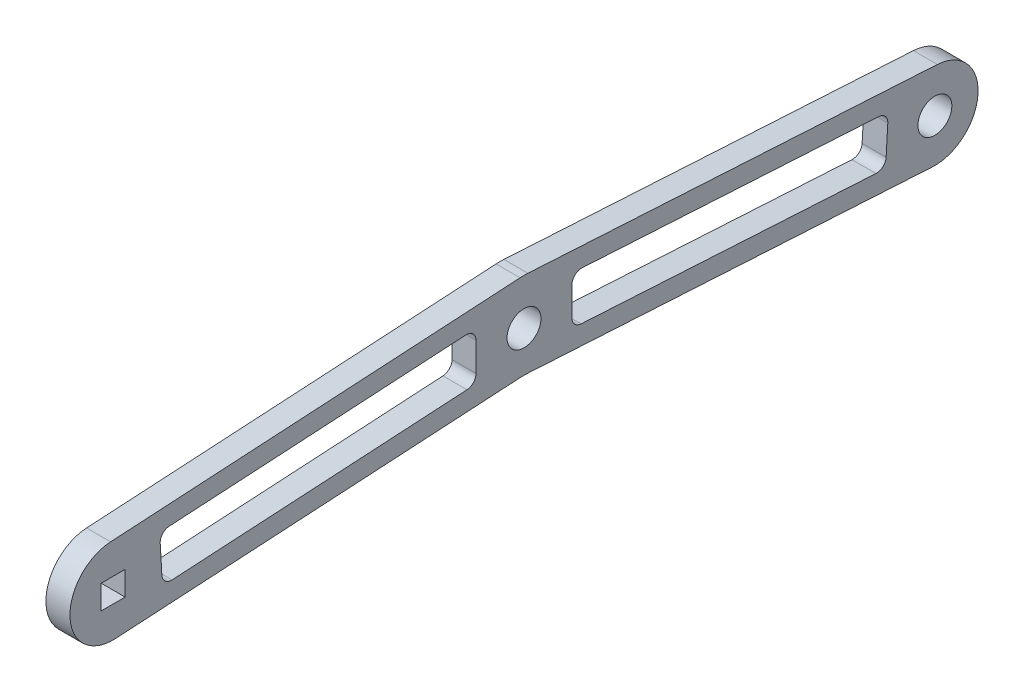
SolidWorks part; units mm, degrees
material "Custom Plastic"
ref_plane "Front Plane" through (0, 0, 0) normal (0, 0, 1) x (1, 0, 0)
ref_plane "Top Plane" through (0, 0, 0) normal (0, 1, 0) x (1, 0, 0)
ref_plane "Right Plane" through (0, 0, 0) normal (1, 0, 0) x (0, 0, -1)
sketch "Sketch1" plane through (0, 0, 0) normal (1, 0, 0) x (0, 0, -1)
  line L0 (0, 0) -> (-108.712, 0) construction
  line L1 (-108.712, 0) -> (-54.356, 3.175) construction
  line L2 (-107.1245, -1.5875) -> (-110.2995, -1.5875)
  line L3 (-107.1245, -1.5875) -> (-107.1245, 1.5875)
  line L4 (-107.1245, 1.5875) -> (-110.2995, 1.5875)
  line L5 (-110.2995, -1.5875) -> (-110.2995, 1.5875)
  line L6 (-107.1245, -1.5875) -> (-110.2995, 1.5875) construction
  line L7 (-107.1245, 1.5875) -> (-110.2995, -1.5875) construction
  line L8 (1.5875, -1.5875) -> (-1.5875, -1.5875) construction
  line L9 (1.5875, -1.5875) -> (1.5875, 1.5875) construction
  line L10 (1.5875, 1.5875) -> (-1.5875, 1.5875) construction
  line L11 (-1.5875, -1.5875) -> (-1.5875, 1.5875) construction
  line L12 (1.5875, -1.5875) -> (-1.5875, 1.5875) construction
  line L13 (1.5875, 1.5875) -> (-1.5875, -1.5875) construction
  line L14 (-54.356, 3.175) -> (0, 0) construction
  line L15 (-109.0453, 5.7053) -> (-54.8744, 8.8695)
  line L16 (-53.8376, 8.8695) -> (0.3333, 5.7053)
  line L17 (0.3333, 5.7053) -> (-0.3333, -5.7053) construction
  line L18 (-0.3333, -5.7053) -> (-53.8376, -2.58)
  line L19 (-54.8744, -2.58) -> (-108.3787, -5.7053)
  line L20 (-109.0453, 5.7053) -> (-108.3787, -5.7053) construction
  line L21 (-102.4839, 2.272) -> (-102.2617, -1.5315)
  line L22 (-100.9198, -2.7253) -> (-61.9019, -0.4462)
  line L23 (-46.8101, -0.4462) -> (-7.7922, -2.7253)
  line L24 (-6.4503, -1.5315) -> (-6.2281, 2.272)
  line L25 (-7.4219, 3.6139) -> (-46.6619, 5.906)
  line L26 (-62.0501, 5.906) -> (-101.2901, 3.6139)
  line L27 (-54.356, 6.3554) -> (-54.356, 3.175) construction
  line L28 (-54.356, 3.175) -> (-54.356, -0.0054) construction
  line L29 (-60.706, 4.6382) -> (-60.706, 0.8217)
  line L30 (-60.706, -0.3763) -> (-54.356, -0.0054) construction
  line L31 (-48.006, 0.8217) -> (-48.006, 4.6382)
  line L32 (-54.356, -0.0054) -> (-48.006, -0.3763) construction
  line L33 (-60.706, 5.9845) -> (-54.356, 6.3554) construction
  line L34 (-54.356, 6.3554) -> (-48.006, 5.9845) construction
  line L35 (-60.706, 3.175) -> (-54.356, 3.175) construction
  line L36 (-54.356, 3.175) -> (-48.006, 3.175) construction
  line L37 (-54.356, 5.0746) -> (-54.356, 8.8846) construction
  circle A0 centre (0, 0) radius 2.2451
  arc A1 (-109.0453, 5.7053) -> (-108.3787, -5.7053) centre (-108.712, 0) ccw
  arc A2 (0.3333, 5.7053) -> (-0.3333, -5.7053) centre (0, 0) cw
  arc A3 (-53.8376, -2.58) -> (-54.8744, -2.58) centre (-54.356, -11.4549) ccw
  arc A4 (-54.8744, 8.8695) -> (-53.8376, 8.8695) centre (-54.356, -0.0054) cw
  arc A5 (-102.4839, 2.272) -> (-101.2901, 3.6139) centre (-101.2161, 2.3461) cw
  arc A6 (-102.2617, -1.5315) -> (-100.9198, -2.7253) centre (-100.9939, -1.4574) ccw
  arc A7 (-7.7922, -2.7253) -> (-6.4503, -1.5315) centre (-7.7181, -1.4574) ccw
  arc A8 (-6.2281, 2.272) -> (-7.4219, 3.6139) centre (-7.4959, 2.3461) ccw
  arc A9 (-48.006, 4.6382) -> (-46.6619, 5.906) centre (-46.736, 4.6382) cw
  arc A10 (-46.8101, -0.4462) -> (-48.006, 0.8217) centre (-46.736, 0.8217) cw
  arc A11 (-60.706, 0.8217) -> (-61.9019, -0.4462) centre (-61.976, 0.8217) cw
  arc A12 (-60.706, 4.6382) -> (-62.0501, 5.906) centre (-61.976, 4.6382) ccw
  circle A13 centre (-54.356, 2.8295) radius 2.2451
  dimension "D6" = 6.35
  dimension "D5" = 8.89
  dimension "D7" = 1.27
  dimension "D9" = 3.81
  dimension "D1" = 108.712
  dimension "D2" = 3.175
  dimension "D3" = 3.175
  dimension "D4" = 5.715
  dimension "D8" = 6.35
extrude "Boss-Extrude1" add sketch "Sketch1" along normal blind 3.175
